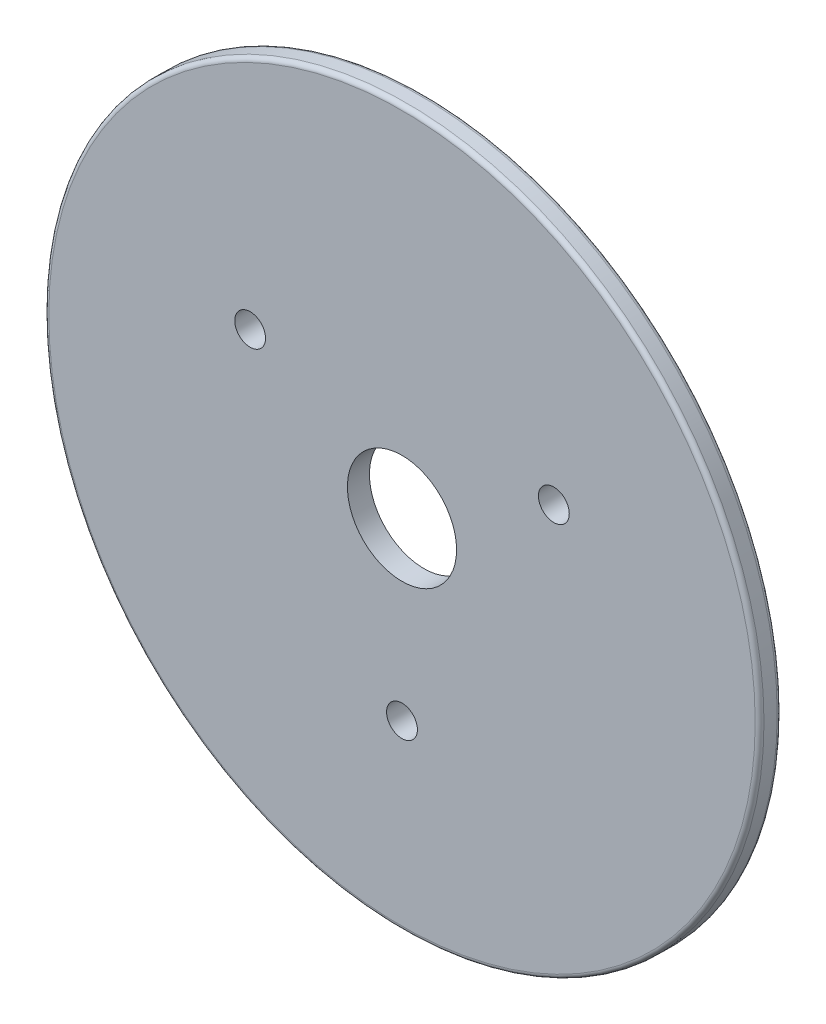
SolidWorks part; units mm, degrees
ref_plane "Front Plane" through (0, 0, 0) normal (0, 0, 1) x (1, 0, 0)
ref_plane "Top Plane" through (0, 0, 0) normal (0, 1, 0) x (1, 0, 0)
ref_plane "Right Plane" through (0, 0, 0) normal (1, 0, 0) x (0, 0, -1)
sketch "Sketch1" plane through (0, 0, 0) normal (0, 1, 0) x (1, 0, 0)
  line L0 (0, 36.1296) -> (0, -19.4741) construction
sketch "Sketch7" plane through (0, 0, 0) normal (0, 0, 1) x (1, 0, 0)
  line L0 (0, 0) -> (0, 34.591) construction
  line L1 (-2.325, 35.546) -> (-2.9401, 37.236) construction
  line L2 (-2.325, 35.546) -> (-1.6298, 33.636) construction
  line L3 (-1.6298, 33.636) -> (1.6298, 33.636) construction
  line L4 (1.6298, 33.636) -> (2.325, 35.546) construction
  line L5 (2.325, 35.546) -> (-2.325, 35.546) construction
  line L6 (0, 33.636) -> (0, 35.546) construction
  line L7 (2.325, 35.546) -> (2.9401, 37.236) construction
  line L8 (-2.9401, 37.236) -> (2.9401, 37.236) construction
  line L9 (0, 0) -> (8.9528, 33.4123) construction
  line L10 (8.9528, 33.4123) -> (9.2196, 34.4082) construction
  line L11 (0, 35.546) -> (0, 35.622) construction
  line L12 (0, 35.622) -> (0, 37.3519) construction
  line L13 (0, 36.4869) -> (9.4435, 35.2437) construction
  line L14 (9.2196, 34.4082) -> (9.6674, 36.0792) construction
  circle A1 centre (0, 0) radius 34.591 construction
  circle A2 centre (-1.2727, 34.146) radius 0.51 construction
  circle A3 centre (1.2727, 34.146) radius 0.51 construction
  circle A4 centre (0, 0) radius 35.622
  circle A5 centre (0, 0) radius 37.3519 construction
  dimension "D3" = 40
  dimension "D6" = 1.02
  dimension "D1" = 3.6
  dimension "D2" = 15
  dimension "D7" = 9.525
  dimension "D4" = 1.91
  dimension "D5" = 4.65
extrude "Boss-Extrude1" add sketch "Sketch7" along normal blind 7.25 and the other way blind 7.25 contours A4 region at (0, 0, 0)
sketch "Sketch14" plane through (0, 0, 0) normal (1, 0, 0) x (0, 0, -1)
  line L0 (-18, 0) -> (-18, 10)
  line L1 (-18, 0) -> (0, 0)
  line L2 (0, 0) -> (0, 19)
  line L3 (0, 19) -> (-7.25, 19)
  line L4 (-7.25, 19) -> (-18, 10)
  line L5 (-7.25, 35.622) -> (-7.25, -35.622) construction
  line L6 (-18, 6.7395) -> (-3.3555, 19) construction
  arc A0 (-7.25, 19) -> (-18, 10) centre (-18.1316, 21.0773) cw
  dimension "D1" = 10
  dimension "D2" = 19
  dimension "D3" = 18
  dimension "D4" = 2.5
revolve "Revolve1" add sketch "Sketch14" angle 360 about L0 region at (0, 7.5733, 7.5341) region at (0, 9.2725, 16.1663) region at (0, 17.2765, 6.6188)
sketch "Sketch9" plane through (0, 0, 0) normal (0, 0, 1) x (1, 0, 0)
  line L0 (2, 0) -> (-2, 0) construction
  line L1 (-2, 0) -> (-2, 7.5) construction
  line L2 (-2, 7.5) -> (2, 7.5) construction
  line L3 (2, 7.5) -> (2, 0) construction
  circle A0 centre (0, 0) radius 6 construction
  dimension "D1" = 12
  dimension "D2" = 4
  dimension "D3" = 7.5
sketch "Sketch10" plane through (0, 0, 0) normal (0, 0, 1) x (1, 0, 0)
  line L0 (2, 0) -> (-2, 0) construction
  line L1 (-2.2, 7.7) -> (2.2, 7.7)
  line L2 (-2.2, 7.7) -> (-2.2, 0)
  line L3 (-2.2, 0) -> (2.2, 0)
  line L4 (2.2, 7.7) -> (2.2, 0)
  line L5 (-2, 7.5) -> (2, 7.5) construction
  line L6 (2, 7.5) -> (2, 0) construction
  circle A0 centre (0, 0) radius 6.2
  circle A1 centre (0, 0) radius 6 construction
  dimension "D1" = 0.2
  dimension "D2" = 0.2
  dimension "D3" = 0.2
extrude "Cut-Extrude3" cut sketch "Sketch10" against normal through all both and the other way through all contours A0 L4 L1 L2 | L2 A0 L4 L3 | L4 A0 L2 L3 region at (0, 6.8793, 0) region at (0, 3.0348, 0) region at (0, -0.8613, 0)
sketch "Sketch11" [suppressed] plane through (0, 0, 0) normal (0, 1, 0) x (1, 0, 0)
  line L0 (29.5757, 7.25) -> (-29.5757, 7.25) construction
  line L1 (11, 7.25) -> (17.5, 7.25)
  line L2 (11, 7.25) -> (11, 4.75)
  line L3 (11, 4.75) -> (17.5, 4.75)
  line L4 (17.5, 7.25) -> (17.5, 4.75)
  line L5 (-29.5757, -7.25) -> (29.5757, -7.25) construction
  line L6 (11, -7.25) -> (17.5, -7.25)
  line L7 (11, -7.25) -> (11, -4.75)
  line L8 (11, -4.75) -> (17.5, -4.75)
  line L9 (17.5, -7.25) -> (17.5, -4.75)
  line L11 (11, 4.75) -> (11, -4.75) construction
  line L12 (17.5, -4.75) -> (17.5, 4.75) construction
  line L13 (6.2, 7.25) -> (-6.2, 7.25) construction
  line L14 (0, 7.25) -> (22.5, 7.25)
  line L15 (0, 7.25) -> (0, -7.25)
  line L16 (0, -7.25) -> (22.5, -7.25)
  line L17 (22.5, 7.25) -> (22.5, -7.25)
  line L18 (-6.2, -7.25) -> (6.2, -7.25) construction
  line L19 (6, 7.25) -> (6, -7.25) construction
  dimension "D1" = 22.5
  dimension "D2" = 6
  dimension "D3" = 5
  dimension "D4" = 5
  dimension "D5" = 2.5
sketch "Sketch15" plane through (0, 0, -7.25) normal (0, 0, -1) x (-1, 0, 0)
  circle A0 centre (0, 0) radius 8.0081
  circle A1 centre (0, 0) radius 2.25
  dimension "D1" = 4.5
extrude "Boss-Extrude2" add sketch "Sketch15" against normal blind 5.5
sketch "Sketch16" plane through (0, 0, -7.25) normal (0, 0, -1) x (-1, 0, 0)
  circle A0 centre (0, 0) radius 5
  dimension "D1" = 10
extrude "Cut-Extrude4" cut sketch "Sketch16" against normal blind 3
sketch "Sketch17" plane through (0, 0, -7.25) normal (0, 0, -1) x (-1, 0, 0)
  circle A0 centre (0, 0) radius 35.622
  circle A1 centre (0, 0) radius 35.622 construction
  circle A2 centre (0, 0) radius 5
  circle A3 centre (0, 0) radius 5 construction
extrude "Boss-Extrude3" add sketch "Sketch17" along normal blind 7.5
sketch "Sketch8" plane through (0, 0, 0) normal (0, 0, 1) x (1, 0, 0)
  line L6 (-1.6298, 33.636) -> (-2.3526, 35.622)
  line L7 (-2.3526, 35.622) -> (2.3526, 35.622)
  line L8 (2.3526, 35.622) -> (1.6298, 33.636)
  line L9 (1.6298, 33.636) -> (-1.6298, 33.636)
  line L10 (-2.325, 35.546) -> (-1.6298, 33.636) construction
  line L11 (1.6298, 33.636) -> (2.325, 35.546) construction
  line L12 (7.1314, 32.9117) -> (6.9472, 35.0171)
  line L13 (6.9472, 35.0171) -> (11.4921, 33.7993)
  line L14 (11.4921, 33.7993) -> (10.2799, 32.0681)
  line L15 (10.2799, 32.0681) -> (7.1314, 32.9117)
  line L16 (15.4065, 29.9445) -> (15.7735, 32.0258)
  line L17 (15.7735, 32.0258) -> (19.8484, 29.6732)
  line L18 (19.8484, 29.6732) -> (18.2295, 28.3147)
  line L19 (18.2295, 28.3147) -> (15.4065, 29.9445)
  line L20 (22.6318, 24.9367) -> (23.525, 26.8521)
  line L21 (23.525, 26.8521) -> (26.8521, 23.525)
  line L22 (26.8521, 23.525) -> (24.9367, 22.6318)
  line L23 (24.9367, 22.6318) -> (22.6318, 24.9367)
  line L24 (28.3147, 18.2295) -> (29.6732, 19.8484)
  line L25 (29.6732, 19.8484) -> (32.0258, 15.7735)
  line L26 (32.0258, 15.7735) -> (29.9445, 15.4065)
  line L27 (29.9445, 15.4065) -> (28.3147, 18.2295)
  line L28 (32.0681, 10.2799) -> (33.7993, 11.4921)
  line L29 (33.7993, 11.4921) -> (35.0171, 6.9472)
  line L30 (35.0171, 6.9472) -> (32.9117, 7.1314)
  line L31 (32.9117, 7.1314) -> (32.0681, 10.2799)
  line L32 (33.636, 1.6298) -> (35.622, 2.3526)
  line L33 (35.622, 2.3526) -> (35.622, -2.3526)
  line L34 (35.622, -2.3526) -> (33.636, -1.6298)
  line L35 (33.636, -1.6298) -> (33.636, 1.6298)
  line L36 (32.9117, -7.1314) -> (35.0171, -6.9472)
  line L37 (35.0171, -6.9472) -> (33.7993, -11.4921)
  line L38 (33.7993, -11.4921) -> (32.0681, -10.2799)
  line L39 (32.0681, -10.2799) -> (32.9117, -7.1314)
  line L40 (29.9445, -15.4065) -> (32.0258, -15.7735)
  line L41 (32.0258, -15.7735) -> (29.6732, -19.8484)
  line L42 (29.6732, -19.8484) -> (28.3147, -18.2295)
  line L43 (28.3147, -18.2295) -> (29.9445, -15.4065)
  line L44 (24.9367, -22.6318) -> (26.8521, -23.525)
  line L45 (26.8521, -23.525) -> (23.525, -26.8521)
  line L46 (23.525, -26.8521) -> (22.6318, -24.9367)
  line L47 (22.6318, -24.9367) -> (24.9367, -22.6318)
  line L48 (18.2295, -28.3147) -> (19.8484, -29.6732)
  line L49 (19.8484, -29.6732) -> (15.7735, -32.0258)
  line L50 (15.7735, -32.0258) -> (15.4065, -29.9445)
  line L51 (15.4065, -29.9445) -> (18.2295, -28.3147)
  line L52 (10.2799, -32.0681) -> (11.4921, -33.7993)
  line L53 (11.4921, -33.7993) -> (6.9472, -35.0171)
  line L54 (6.9472, -35.0171) -> (7.1314, -32.9117)
  line L55 (7.1314, -32.9117) -> (10.2799, -32.0681)
  line L56 (1.6298, -33.636) -> (2.3526, -35.622)
  line L57 (2.3526, -35.622) -> (-2.3526, -35.622)
  line L58 (-2.3526, -35.622) -> (-1.6298, -33.636)
  line L59 (-1.6298, -33.636) -> (1.6298, -33.636)
  line L60 (-7.1314, -32.9117) -> (-6.9472, -35.0171)
  line L61 (-6.9472, -35.0171) -> (-11.4921, -33.7993)
  line L62 (-11.4921, -33.7993) -> (-10.2799, -32.0681)
  line L63 (-10.2799, -32.0681) -> (-7.1314, -32.9117)
  line L64 (-15.4065, -29.9445) -> (-15.7735, -32.0258)
  line L65 (-15.7735, -32.0258) -> (-19.8484, -29.6732)
  line L66 (-19.8484, -29.6732) -> (-18.2295, -28.3147)
  line L67 (-18.2295, -28.3147) -> (-15.4065, -29.9445)
  line L68 (-22.6318, -24.9367) -> (-23.525, -26.8521)
  line L69 (-23.525, -26.8521) -> (-26.8521, -23.525)
  line L70 (-26.8521, -23.525) -> (-24.9367, -22.6318)
  line L71 (-24.9367, -22.6318) -> (-22.6318, -24.9367)
  line L72 (-28.3147, -18.2295) -> (-29.6732, -19.8484)
  line L73 (-29.6732, -19.8484) -> (-32.0258, -15.7735)
  line L74 (-32.0258, -15.7735) -> (-29.9445, -15.4065)
  line L75 (-29.9445, -15.4065) -> (-28.3147, -18.2295)
  line L76 (-32.0681, -10.2799) -> (-33.7993, -11.4921)
  line L77 (-33.7993, -11.4921) -> (-35.0171, -6.9472)
  line L78 (-35.0171, -6.9472) -> (-32.9117, -7.1314)
  line L79 (-32.9117, -7.1314) -> (-32.0681, -10.2799)
  line L80 (-33.636, -1.6298) -> (-35.622, -2.3526)
  line L81 (-35.622, -2.3526) -> (-35.622, 2.3526)
  line L82 (-35.622, 2.3526) -> (-33.636, 1.6298)
  line L83 (-33.636, 1.6298) -> (-33.636, -1.6298)
  line L84 (-32.9117, 7.1314) -> (-35.0171, 6.9472)
  line L85 (-35.0171, 6.9472) -> (-33.7993, 11.4921)
  line L86 (-33.7993, 11.4921) -> (-32.0681, 10.2799)
  line L87 (-32.0681, 10.2799) -> (-32.9117, 7.1314)
  line L88 (-29.9445, 15.4065) -> (-32.0258, 15.7735)
  line L89 (-32.0258, 15.7735) -> (-29.6732, 19.8484)
  line L90 (-29.6732, 19.8484) -> (-28.3147, 18.2295)
  line L91 (-28.3147, 18.2295) -> (-29.9445, 15.4065)
  line L92 (-24.9367, 22.6318) -> (-26.8521, 23.525)
  line L93 (-26.8521, 23.525) -> (-23.525, 26.8521)
  line L94 (-23.525, 26.8521) -> (-22.6318, 24.9367)
  line L95 (-22.6318, 24.9367) -> (-24.9367, 22.6318)
  line L96 (-18.2295, 28.3147) -> (-19.8484, 29.6732)
  line L97 (-19.8484, 29.6732) -> (-15.7735, 32.0258)
  line L98 (-15.7735, 32.0258) -> (-15.4065, 29.9445)
  line L99 (-15.4065, 29.9445) -> (-18.2295, 28.3147)
  line L100 (-10.2799, 32.0681) -> (-11.4921, 33.7993)
  line L101 (-11.4921, 33.7993) -> (-6.9472, 35.0171)
  line L102 (-6.9472, 35.0171) -> (-7.1314, 32.9117)
  line L103 (-7.1314, 32.9117) -> (-10.2799, 32.0681)
  circle A0 centre (0, 0) radius 35.622 construction
  point P119 (0, 0)
  dimension "D1" = 24
extrude "Cut-Extrude2" cut sketch "Sketch8" against normal through all both and the other way through all
fillet "Fillet2" radius 0.51 96 edges at (-19.7865, -29.6212, -3.75) (-15.7595, -31.9462, -3.75) (-11.4458, -33.7331, -3.75) (-6.9542, -34.9366, -3.75) (-2.325, -35.546, -3.75) (2.325, -35.546, -3.75) (6.9542, -34.9366, -3.75) (11.4458, -33.7331, -3.75) (15.7595, -31.9462, -3.75) (19.7865, -29.6212, -3.75) (23.4908, -26.7788, -3.75) (26.7788, -23.4908, -3.75) (29.6212, -19.7865, -3.75) (31.9462, -15.7595, -3.75) (33.7331, -11.4458, -3.75) (34.9366, -6.9542, -3.75) (35.546, -2.325, -3.75) (35.546, 2.325, -3.75) (34.9366, 6.9542, -3.75) (33.7331, 11.4458, -3.75) (31.9462, 15.7595, -3.75) (29.6212, 19.7865, -3.75) (26.7788, 23.4908, -3.75) (23.4908, 26.7788, -3.75) (19.7865, 29.6212, -3.75) (15.7595, 31.9462, -3.75) (11.4458, 33.7331, -3.75) (6.9542, 34.9366, -3.75) (2.325, 35.546, -3.75) (-18.2295, -28.3147, -3.75) (-15.4065, -29.9445, -3.75) (-10.2799, -32.0681, -3.75) (-7.1314, -32.9117, -3.75) (-1.6298, -33.636, -3.75) (1.6298, -33.636, -3.75) (7.1314, -32.9117, -3.75) (10.2799, -32.0681, -3.75) (15.4065, -29.9445, -3.75) (18.2295, -28.3147, -3.75) (22.6318, -24.9367, -3.75) (24.9367, -22.6318, -3.75) (28.3147, -18.2295, -3.75) (29.9445, -15.4065, -3.75) (32.0681, -10.2799, -3.75) (32.9117, -7.1314, -3.75) (33.636, -1.6298, -3.75) (33.636, 1.6298, -3.75) (32.9117, 7.1314, -3.75) (32.0681, 10.2799, -3.75) (29.9445, 15.4065, -3.75) (28.3147, 18.2295, -3.75) (24.9367, 22.6318, -3.75) (22.6318, 24.9367, -3.75) (18.2295, 28.3147, -3.75) (15.4065, 29.9445, -3.75) (10.2799, 32.0681, -3.75) (7.1314, 32.9117, -3.75) (1.6298, 33.636, -3.75) (-1.6298, 33.636, -3.75) (-2.325, 35.546, -3.75) (-33.7331, 11.4458, -3.75) (-32.0681, 10.2799, -3.75) (-32.9117, 7.1314, -3.75) (-34.9366, 6.9542, -3.75) (-35.546, 2.325, -3.75) (-33.636, 1.6298, -3.75) (-33.636, -1.6298, -3.75) (-35.546, -2.325, -3.75) (-34.9366, -6.9542, -3.75) (-32.9117, -7.1314, -3.75) (-32.0681, -10.2799, -3.75) (-33.7331, -11.4458, -3.75) (-31.9462, -15.7595, -3.75) (-29.9445, -15.4065, -3.75) (-28.3147, -18.2295, -3.75) (-29.6212, -19.7865, -3.75) (-26.7788, -23.4908, -3.75) (-24.9367, -22.6318, -3.75) (-22.6318, -24.9367, -3.75) (-23.4908, -26.7788, -3.75) (-31.9462, 15.7595, -3.75) (-29.9445, 15.4065, -3.75) (-28.3147, 18.2295, -3.75) (-29.6212, 19.7865, -3.75) (-26.7788, 23.4908, -3.75) (-24.9367, 22.6318, -3.75) (-22.6318, 24.9367, -3.75) (-23.4908, 26.7788, -3.75) (-19.7865, 29.6212, -3.75) (-18.2295, 28.3147, -3.75) (-15.4065, 29.9445, -3.75) (-15.7595, 31.9462, -3.75) (-11.4458, 33.7331, -3.75) (-10.2799, 32.0681, -3.75) (-7.1314, 32.9117, -3.75) (-6.9542, 34.9366, -3.75)
sketch "Sketch18" plane through (0, 0, -14.75) normal (0, 0, -1) x (-1, 0, 0)
  circle A0 centre (0, 0) radius 5
  circle A1 centre (0, 0) radius 40.622
  circle A2 centre (0, 0) radius 35.622
  circle A3 centre (0, 0) radius 5 construction
  circle A4 centre (0, 0) radius 35.622 construction
  dimension "D1" = 5
extrude "Boss-Extrude4" add sketch "Sketch18" along normal blind 2.5 contours A1 A2 | A2 A0 region at (39.473, 0, -14.75) region at (34.6144, 0, -14.75)
sketch "Sketch19" plane through (0, 0, 7.25) normal (0, 0, 1) x (1, 0, 0)
  circle A0 centre (0, 0) radius 19
  circle A1 centre (0, 0) radius 40.622
  circle A2 centre (0, 0) radius 40.622 construction
  circle A3 centre (0, 0) radius 19 construction
extrude "Boss-Extrude5" add sketch "Sketch19" against normal blind 2.5
sketch "Sketch20" plane through (0, 0, 18) normal (0, 0, 1) x (1, 0, 0)
  line L0 (-2.2, 5.7966) -> (-2.2, 7.7)
  line L1 (-2.2, 7.7) -> (2.2, 7.7)
  line L2 (-2.2, 7.7) -> (2.2, 7.7) construction
  line L3 (2.2, 7.7) -> (2.2, 5.7966)
  circle A0 centre (0, 0) radius 6.2
  arc A1 (-2.2, 5.7966) -> (2.2, 5.7966) centre (0, 0) ccw construction
  arc M2 (2.2, 5.7966) -> (-2.2, 5.7966) centre (0, 0) cw
  line M3 (-2.2, 5.7966) -> (-2.2, 7.7)
  line M4 (-2.2, 7.7) -> (2.2, 7.7)
  line M5 (2.2, 7.7) -> (2.2, 5.7966)
extrude "Cut-Extrude5" cut sketch "Sketch20" against normal through all contours A0 M5 M4 M3 | A0 M2 region at (0, 6.8793, 18) region at (0, 0, 18)
fillet "Fillet3" radius 0.5 12 edges at (2.2, 5.7966, 0.375) (-2.2, 5.7966, 0.375) (2.2, 6.7483, 18) (-2.2, 6.7483, 18) (0, 7.7, 18) (-19, 0, 7.25) (-10, 0, 18) (0, -6.2, 18) (40.622, 0, 4.75) (-40.622, 0, -14.75) (-40.622, 0, -17.25) (40.622, 0, 7.25)
ref_plane "Plane1" through (0, 0, -5.25) normal (0, 0, 1) x (1, 0, 0)
sketch "Sketch21" plane through (0, 0, -5.25) normal (0, 0, 1) x (1, 0, 0)
  circle A0 centre (0, 0) radius 8.0081
  circle A1 centre (0, 0) radius 2.25
  circle A2 centre (0, 0) radius 6.2
  arc A3 (-2.4985, 5.6743) -> (2.4985, 5.6743) centre (0, 0) ccw construction
  dimension "D1" = 4.5
extrude "Boss-Extrude6" add sketch "Sketch21" against normal blind 2.5 contours A2 A1 | A0 A2 region at (-7.7816, 0, -5.25) region at (-6.0246, 0, -5.25)
extrude "Boss-Extrude7" add sketch "Sketch21<4>" against normal up to surface (12 mm away) contours A0 A2 region at (-7.7816, 0, -5.25) up to face at (-40.122, 0, -17.25)
sketch "Sketch21<4>" plane through (0, 0, -5.25) normal (0, 0, 1) x (1, 0, 0) same geometry as "Sketch21"
sketch "Sketch23" plane through (0, 0, -14.75) normal (0, 0, 1) x (1, 0, 0)
  line L0 (0, 33.636) -> (0, 6.2) construction
  line L2 (1.2727, 33.636) -> (-1.2727, 33.636) construction
  circle A0 centre (0, 0) radius 19.918 construction
  circle A1 centre (0, 0) radius 6.2 construction
  circle A2 centre (0, -19.918) radius 1.75
  circle A3 centre (-17.2495, 9.959) radius 1.75
  circle A4 centre (17.2495, 9.959) radius 1.75
  point P10 (0, 19.918)
  point P19 (0, 0)
  point P26 (0, 0)
  dimension "D1" = 3.5
  dimension "D2" = 3
extrude "Cut-Extrude7" cut sketch "Sketch23" along normal blind 10 and the other way through all
ref_plane "Plane2" through (0, 0, -12.25) normal (0, 0, 1) x (1, 0, 0)
sketch "Sketch24" plane through (0, 0, -12.25) normal (0, 0, 1) x (1, 0, 0)
  line L0 (0, -19.918) -> (0, 0) construction
  line L1 (-17.2495, 6.6104) -> (-14.3495, 8.2847)
  line L2 (-14.3495, 8.2847) -> (-14.3495, 11.6333)
  line L3 (-14.3495, 11.6333) -> (-17.2495, 13.3076)
  line L4 (-17.2495, 13.3076) -> (-20.1495, 11.6333)
  line L5 (-20.1495, 11.6333) -> (-20.1495, 8.2847)
  line L6 (-20.1495, 8.2847) -> (-17.2495, 6.6104)
  line L7 (2.9, -21.5923) -> (2.9, -18.2437)
  line L8 (2.9, -18.2437) -> (0, -16.5694)
  line L9 (0, -16.5694) -> (-2.9, -18.2437)
  line L10 (-2.9, -18.2437) -> (-2.9, -21.5923)
  line L11 (-2.9, -21.5923) -> (0, -23.2666)
  line L12 (0, -23.2666) -> (2.9, -21.5923)
  line L13 (17.2495, 6.6104) -> (20.1495, 8.2847)
  line L14 (20.1495, 8.2847) -> (20.1495, 11.6333)
  line L15 (20.1495, 11.6333) -> (17.2495, 13.3076)
  line L16 (17.2495, 13.3076) -> (14.3495, 11.6333)
  line L17 (14.3495, 11.6333) -> (14.3495, 8.2847)
  line L18 (14.3495, 8.2847) -> (17.2495, 6.6104)
  line L19 (0, 0) -> (17.2495, 9.959) construction
  line L21 (-17.2495, 9.959) -> (0, 0) construction
  circle A0 centre (-17.2495, 9.959) radius 2.9 construction
  circle A1 centre (0, -19.918) radius 2.9 construction
  circle A2 centre (17.2495, 9.959) radius 2.9 construction
  dimension "D1" = 5.8
extrude "Cut-Extrude8" cut sketch "Sketch24" along normal blind 3 contours L13 L14 L15 L16 | L13 L16 L17 L18 | L3 L4 L5 L6 | L3 L6 L1 L2 | L10 L7 L8 L9 | L10 L11 L12 L7 region at (-17.2495, 9.959, -12.25) region at (0, -19.918, -12.25) region at (17.2495, 9.959, -12.25)
sketch "Sketch25" plane through (0, 0, -9.25) normal (0, 0, -1) x (-1, 0, 0)
  circle A0 centre (0, -19.918) radius 1.75
  circle A1 centre (17.2495, 9.959) radius 1.75
  circle A2 centre (-17.2495, 9.959) radius 1.75
  circle A3 centre (0, -19.918) radius 1.75 construction
extrude "Boss-Extrude8" add sketch "Sketch25" against normal blind 0.2
sketch "Sketch22" plane through (0, 0, 0) normal (0, 1, 0) x (1, 0, 0)
  line L0 (40.622, 15.25) -> (40.622, 16.75) construction
  line L1 (-40.622, 17.25) -> (40.622, 17.25)
  line L2 (-40.622, 17.25) -> (-40.622, 14.75)
  line L3 (-40.622, 14.75) -> (40.622, 14.75)
  line L4 (40.622, 17.25) -> (40.622, 14.75)
  line L5 (-40.622, 17.25) -> (40.622, 14.75) construction
  line L6 (-40.622, 14.75) -> (40.622, 17.25) construction
  line L7 (-32.1547, -18) -> (32.1547, -18) construction
  line L8 (-40.622, 14.75) -> (40.622, 14.75)
  line L9 (-40.622, 14.75) -> (-40.622, -18)
  line L10 (-40.622, -18) -> (40.622, -18)
  line L11 (40.622, 14.75) -> (40.622, -18)
  line L12 (-40.122, 14.75) -> (40.122, 14.75) construction
  line L13 (1.75, 17.25) -> (-1.75, 17.25) construction
  line L14 (-40.622, 16.75) -> (-40.622, 15.25) construction
  point P0 (0, 16)
extrude "Cut-Extrude10" cut sketch "Sketch22" against normal through all both and the other way through all contours L11 L3 L9 L10 region at (0, 0, 1.625)
